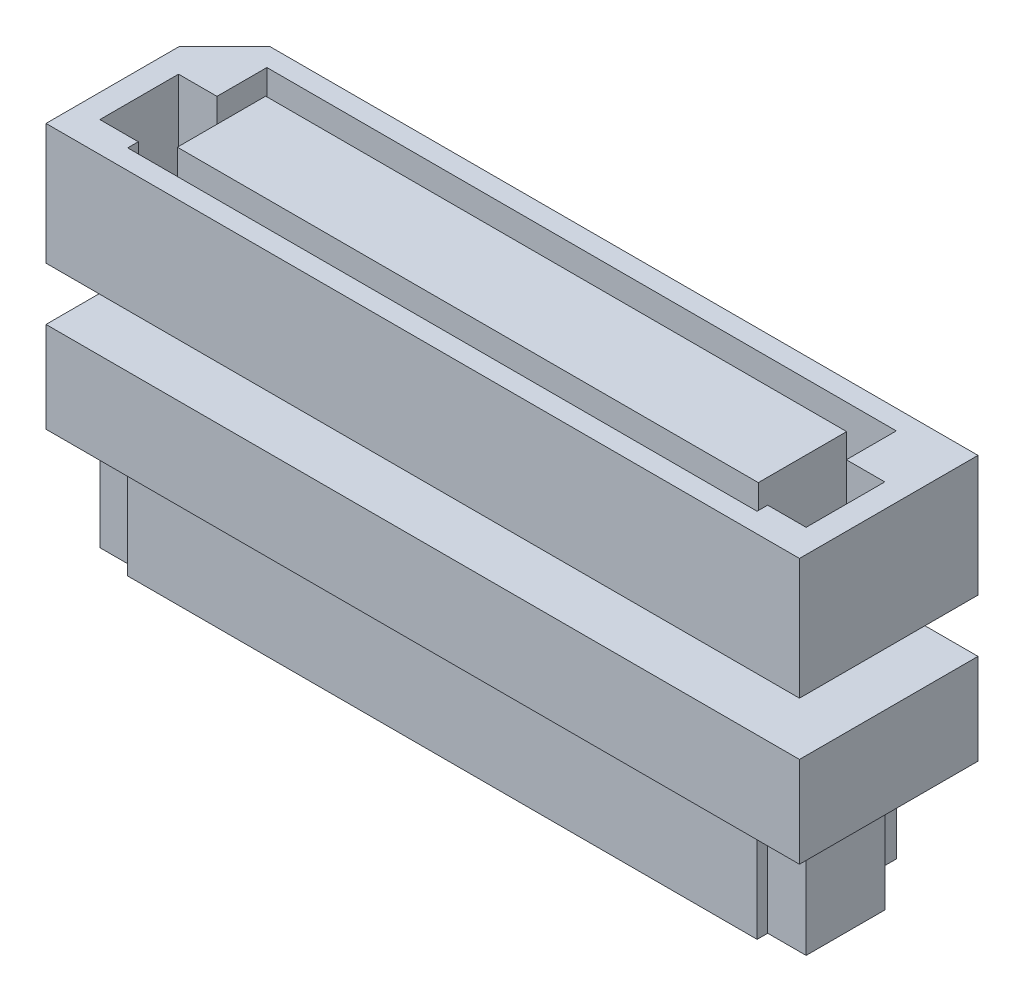
SolidWorks part; units mm, degrees
ref_plane "Front Plane" through (0, 0, 0) normal (0, 0, 1) x (1, 0, 0)
ref_plane "top-of-PCB" through (0, 0, 0) normal (0, 1, 0) x (1, 0, 0)
ref_plane "Right Plane" through (0, 0, 0) normal (1, 0, 0) x (0, 0, -1)
ref_plane "bottom-of-PCB" through (0, -1.7526, 0) normal (0, 1, 0) x (1, 0, 0)
ref_plane "center-of-slot" through (0, -0.8763, 0) normal (0, 1, 0) x (1, 0, 0)
sketch "all-outlines" [suppressed] plane through (0, 0, 0) normal (0, 1, 0) x (1, 0, 0)
  line L0 (-21.4847, 2.95) -> (-21.4847, -2.95) construction
  line L1 (24.45, 2.95) -> (-24.45, 2.95) construction
  line L2 (24.45, 2.95) -> (24.45, -2.95) construction
  line L3 (24.45, -2.95) -> (-24.45, -2.95) construction
  line L4 (-24.45, 2.95) -> (-24.45, -2.95) construction
  line L5 (-18.4847, 2.95) -> (-18.4847, -2.95) construction
  line L6 (12.45, 2.95) -> (12.45, -2.95) construction
  line L7 (-15.45, 2.95) -> (-15.45, -2.95) construction
  line L8 (-24.45, 1.8521) -> (24.45, 1.8521) construction
  line L9 (-12.45, 2.95) -> (-12.45, -2.95) construction
  line L10 (-23.3893, 2.95) -> (-24.45, 1.8521) construction
  line L11 (21.45, -2.95) -> (21.45, 2.95) construction
  line L12 (-21.4847, 1.8521) -> (-20.424, 2.95) construction
  line L13 (15.45, -2.95) -> (15.45, 2.95) construction
  line L14 (-18.4847, 1.8521) -> (-17.4626, 2.95) construction
  line L15 (18.45, -2.95) -> (18.45, 2.95) construction
  line L16 (-15.45, 1.8521) -> (-14.4279, 2.95) construction
  line L18 (-12.45, 1.8521) -> (-11.4279, 2.95) construction
sketch "Sketch14" plane through (0, 0, 0) normal (1, 0, 0) x (0, 0, -1)
  line L1 (2.95, 0) -> (-2.95, 0)
  line L2 (2.95, 0) -> (2.95, 4)
  line L3 (2.95, 4) -> (-2.95, 4)
  line L4 (-2.95, 0) -> (-2.95, 4)
  line L5 (-2.3, 4) -> (2.3, 4) construction
  line L6 (-2.3, 4) -> (-2.3, 0.5) construction
  line L7 (-2.3, 0.5) -> (2.3, 0.5) construction
  line L8 (2.3, 4) -> (2.3, 0.5) construction
  line L9 (-1.95, 4) -> (0.65, 4) construction
  line L10 (-1.95, 4) -> (-1.95, 0.5) construction
  line L11 (-1.95, 0.5) -> (0.65, 0.5) construction
  line L12 (0.65, 4) -> (0.65, 0.5) construction
  line L13 (1.46, 4) -> (-1.46, 4) construction
  line L14 (1.46, 4) -> (1.46, 0.5) construction
  line L15 (1.46, 0.5) -> (-1.46, 0.5) construction
  line L16 (-1.46, 4) -> (-1.46, 0.5) construction
extrude "body" add sketch "Sketch14" against normal blind 12.45 separate body
ref_plane "for-slot-a" through (-10.4, 0, 0) normal (-1, 0, 0) x (0, 0, 1)
sketch "Sketch17" plane through (0, 0, 0) normal (1, 0, 0) x (0, 0, -1)
  line L1 (-2.3, 4) -> (2.3, 4)
  line L2 (-2.3, 4) -> (-2.3, 0.5)
  line L3 (-2.3, 0.5) -> (2.3, 0.5)
  line L4 (2.3, 4) -> (2.3, 0.5)
extrude "slot-a" cut sketch "Sketch17" along normal through all from surface starting at plane "for-slot-a"
ref_plane "for-slot-1" through (-11.67, 0, 0) normal (-1, 0, 0) x (0, 0, 1)
sketch "Sketch18" plane through (0, 0, 0) normal (1, 0, 0) x (0, 0, -1)
  line L1 (-1.95, 4) -> (0.65, 4)
  line L2 (-1.95, 4) -> (-1.95, 0.5)
  line L3 (-1.95, 0.5) -> (0.65, 0.5)
  line L4 (0.65, 4) -> (0.65, 0.5)
extrude "slot-1" cut sketch "Sketch18" along normal through all from surface starting at plane "for-slot-1"
sketch "Sketch23" plane through (0, 0, 0) normal (1, 0, 0) x (0, 0, -1)
  line L1 (-1.46, 4) -> (1.46, 4)
  line L2 (-1.46, 4) -> (-1.46, 0.5)
  line L3 (-1.46, 0.5) -> (1.46, 0.5)
  line L4 (1.46, 4) -> (1.46, 0.5)
ref_plane "for-inner-body" through (-9.6, 0, 0) normal (-1, 0, 0) x (0, 0, 1)
extrude "Boss-Extrude3" add sketch "Sketch23" against normal up to surface (9.6 mm away) up to plane "for-inner-body"
mirror "Mirror2" about plane through (0, 0, 0) normal (1, 0, 0) of bodies 142 136
ref_plane "bevel" through (-7.7, 0, -7.7) normal (-0.7071, 0, -0.7071) x (-0.7071, 0, 0.7071)
sketch "Sketch19" plane through (-7.7, 0, -7.7) normal (-0.7071, 0, -0.7071) x (-0.7071, 0, 0.7071)
  line L1 (3.8193, -0.3384) -> (16.7274, -0.3384)
  line L2 (3.8193, -0.3384) -> (3.8193, 5.046)
  line L3 (3.8193, 5.046) -> (16.7274, 5.046)
  line L4 (16.7274, -0.3384) -> (16.7274, 5.046)
extrude "Cut-Extrude1" cut sketch "Sketch19" along normal through all from offset 1.0608 offset against normal yes
sketch "Sketch20" plane through (0, -1.7526, 0) normal (0, 1, 0) x (1, 0, 0)
  line L0 (-12.45, -2.95) -> (-12.45, 1.4498)
  line L1 (-12.45, 1.4498) -> (-10.9498, 2.95)
  line L2 (-10.9498, 2.95) -> (12.45, 2.95)
  line L3 (12.45, 2.95) -> (12.45, -2.95)
  line L4 (12.45, -2.95) -> (-12.45, -2.95)
extrude "Boss-Extrude1" add sketch "Sketch20" against normal blind 3 separate body
sketch "Sketch22" plane through (0, -4.7526, 0) normal (0, -1, 0) x (1, 0, 0)
  line L0 (10.4, 2.3) -> (10.4, 1.95)
  line L1 (10.4, 1.95) -> (11.67, 1.95)
  line L2 (10.4, 1.95) -> (11.67, 1.95) construction
  line L3 (11.67, 1.95) -> (11.67, -0.65) construction
  line L4 (11.67, 1.95) -> (11.67, -0.65)
  line L5 (11.67, -0.65) -> (10.4, -0.65)
  line L8 (10.4, -0.65) -> (10.4, -2.3)
  line L9 (10.4, -2.3) -> (-10.4, -2.3)
  line L12 (-10.4, 2.2) -> (-10.4, -2.2) construction
  line L14 (10.4, -2.3) -> (-10.4, -2.3) construction
  line L15 (-10.4, -2.3) -> (-10.4, -0.65)
  line L17 (-10.4, -0.65) -> (-11.67, -0.65)
  line L18 (-10.4, -0.65) -> (-11.67, -0.65) construction
  line L19 (-11.67, 2.2) -> (-11.67, -2.2) construction
  line L20 (-11.67, -0.65) -> (-11.67, 1.95)
  line L21 (-11.67, 1.95) -> (-10.4, 1.95)
  line L22 (-10.4, 1.95) -> (-11.67, 1.95) construction
  line L23 (-10.4, 1.95) -> (-10.4, 2.3)
  line L24 (10.4, 2.3) -> (-10.4, 2.3) construction
  line L25 (-10.4, 2.3) -> (10.4, 2.3)
extrude "Boss-Extrude2" add sketch "Sketch22" along normal blind 3.5
sketch "Sketch24" plane through (0, -8.2526, 0) normal (0, -1, 0) x (1, 0, 0)
  line L0 (-9.6, 2.2) -> (-9.6, -2.2) construction
  line L1 (9.6, 1.46) -> (-9.6, 1.46)
  line L2 (9.6, 1.46) -> (9.6, -1.46)
  line L3 (9.6, -1.46) -> (-9.6, -1.46)
  line L4 (-9.6, 1.46) -> (-9.6, -1.46)
  line L5 (-9.6, -1.46) -> (9.6, -1.46) construction
extrude "Cut-Extrude2" cut sketch "Sketch24" against normal blind 3.5
sketch "Sketch26" [suppressed] plane through (0, 4, 0) normal (0, 1, 0) x (1, 0, 0)
  line L0 (12.45, -2.95) -> (12.45, 2.95)
  line L1 (12.45, 2.95) -> (-10.9498, 2.95)
  line L2 (-10.9498, 2.95) -> (-12.45, 1.4498)
  line L3 (-12.45, 1.4498) -> (-12.45, -2.95)
  line L4 (-12.45, -2.95) -> (12.45, -2.95)
  line L5 (10.4, -2.3) -> (10.4, -1.95)
  line L6 (10.4, -1.95) -> (11.67, -1.95)
  line L7 (11.67, -1.95) -> (11.67, 0.65)
  line L8 (11.67, 0.65) -> (10.4, 0.65)
  line L9 (10.4, 0.65) -> (10.4, 2.3)
  line L10 (10.4, 2.3) -> (-10.4, 2.3)
  line L11 (-10.4, 2.3) -> (-10.4, 0.65)
  line L12 (-10.4, 0.65) -> (-11.67, 0.65)
  line L13 (-11.67, 0.65) -> (-11.67, -1.95)
  line L14 (-11.67, -1.95) -> (-10.4, -1.95)
  line L15 (-10.4, -1.95) -> (-10.4, -2.3)
  line L16 (-10.4, -2.3) -> (10.4, -2.3)
  line L17 (9.6, -1.46) -> (9.6, 1.46)
  line L18 (9.6, 1.46) -> (-9.6, 1.46)
  line L19 (-9.6, 1.46) -> (-9.6, -1.46)
  line L20 (-9.6, -1.46) -> (9.6, -1.46)
extrude "Boss-Extrude4" [suppressed] add sketch "Sketch26" along normal blind 5 contours L19 L20 L17 L18
